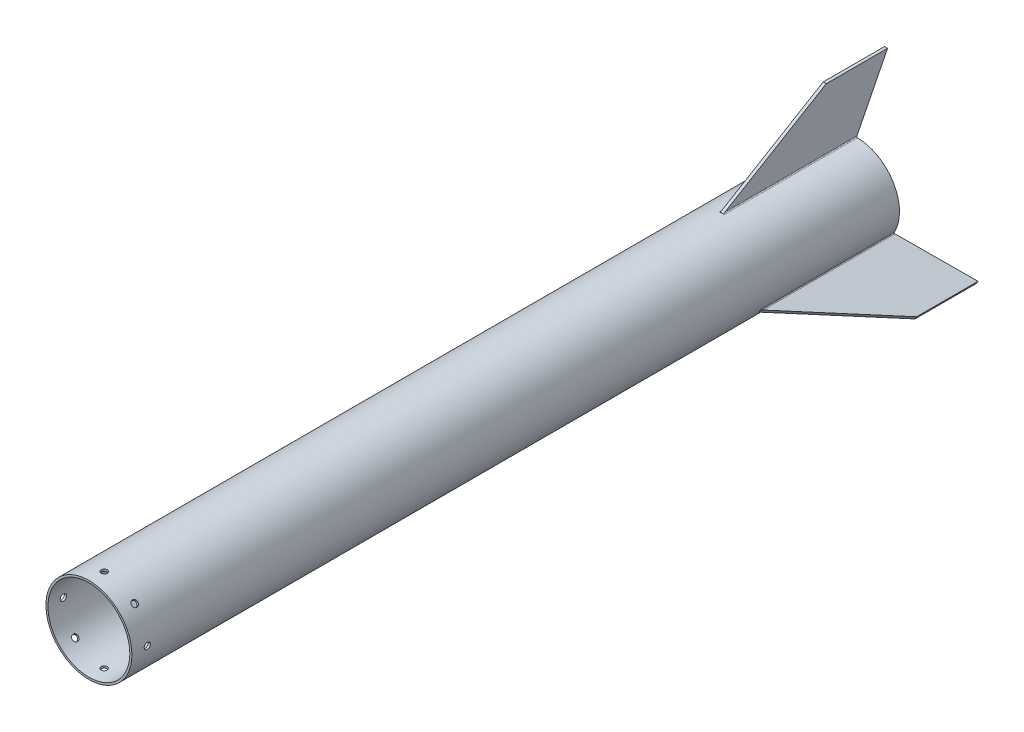
SolidWorks part; units mm, degrees
material "Default"
ref_plane "Front Plane" through (0, 0, 0) normal (0, 0, 1) x (1, 0, 0)
ref_plane "Top Plane" through (0, 0, 0) normal (0, 1, 0) x (1, 0, 0)
ref_plane "Right Plane" through (0, 0, 0) normal (1, 0, 0) x (0, 0, -1)
sketch "Sketch1" plane through (0, 0, 0) normal (0, 0, 1) x (1, 0, 0)
  circle A0 centre (0, 0) radius 42
  circle A1 centre (0, 0) radius 40
  dimension "D1" = 84
  dimension "D2" = 2
extrude "Boss-Extrude1" add sketch "Sketch1" along normal blind 750
ref_plane "Bolts to Avionics" through (45, 0, 0) normal (1, 0, 0) x (0, 0, -1)
ref_plane "Tail bolts" through (-40, 0, 0) normal (1, 0, 0) x (0, 0, -1)
sketch "Sketch2" plane through (45, 0, 0) normal (1, 0, 0) x (0, 0, -1)
  line L0 (-750, 0) -> (-735, 0) construction
  line L1 (-750, 42) -> (-750, -42) construction
  circle A0 centre (-735, 0) radius 3
  dimension "D2" = 6
  dimension "D1" = 15
extrude "Cut-Extrude1" cut sketch "Sketch2" against normal up to surface (5 mm away) up to face at (40, 0, 750)
pattern_circular "CirPattern1" count 8 over 360 about axis through (0, 0, 750) along (0, 0, -1) of "Cut-Extrude1"
sketch "Sketch4" plane through (-40, 0, 0) normal (1, 0, 0) x (0, 0, -1)
  line L0 (0, 0) -> (-20, 0) construction
  circle A0 centre (-20, 0) radius 5
  dimension "D2" = 10
  dimension "D1" = 20
extrude "Cut-Extrude2" cut sketch "Sketch4" along normal up to surface up to face at (-2.9218, -39.8931, 734.3195)
pattern_circular "CirPattern2" count 6 over 360 about axis through (0, 0, 0) along (0, 0, 1) of "Cut-Extrude2"
sketch "Tail Configuration" plane through (0, 0, 0) normal (0, 0, -1) x (-1, 0, 0)
  line L0 (0, 0) -> (0, 42) construction
  line L1 (0, 0) -> (36.3731, -21) construction
  line L2 (0, 0) -> (-36.3731, -21) construction
  line L3 (31.4856, -29.4654) -> (41.2605, -12.5346) construction
  line L4 (-41.8479, -11.5173) -> (-30.8983, -30.4827) construction
  circle A0 centre (0, 0) radius 42 construction
  point P10 (0, 0)
  point P12 (36.3731, -21)
  point P15 (-36.3731, -21)
  dimension "D1" = 3
ref_plane "Fin 1" through (0, 42, 0) normal (0, 1, 0) x (1, 0, 0)
sketch "Sketch6" plane through (0, 42, 0) normal (0, 1, 0) x (1, 0, 0)
  line L4 (0, 0) -> (0, -62.2364) construction
  point P4 (0, 0)
ref_plane "Plane6" through (0, 0, 0) normal (-1, 0, 0) x (0, 0, 1)
sketch "Sketch13" plane through (0, 0, 0) normal (-1, 0, 0) x (0, 0, 1)
  line L0 (0, 42) -> (130, 42) construction
  line L1 (52.1788, 42) -> (-52.1788, 42) construction
  line L2 (130, 42) -> (29.6133, 102)
  line L3 (29.6133, 102) -> (-30.3867, 102)
  line L4 (-30.3867, 102) -> (0, 42)
  line L5 (0, 42) -> (0, 102) construction
  line L6 (97.5, 42) -> (97.5, 50.3814) construction
  line L7 (97.5, 42) -> (14.6133, 102) construction
  line L9 (0, 42) -> (130, 42) construction
  line L10 (0, 42) -> (0, 41)
  line L11 (0, 41) -> (130, 41)
  line L12 (130, 42) -> (130, 41)
  dimension "D5" = 32.5
  dimension "D6" = 15
  dimension "D7" = 1
  dimension "D1" = 60
  dimension "D2" = 130
  dimension "D3" = 60
  dimension "D4" = 54.1
extrude "Boss-Extrude6" add sketch "Sketch13" along normal blind 3
ref_plane "Fin 2" through (-36.3731, -21, 0) normal (0.866, 0.5, 0) x (-0.5, 0.866, 0)
sketch "Sketch9" plane through (-36.3731, -21, 0) normal (0.866, 0.5, 0) x (-0.5, 0.866, 0)
  line L0 (0, 0) -> (0, 21.8091) construction
ref_plane "Plane4" through (0, 0, 0) normal (-0.5, 0.866, 0) x (0, 0, 1)
sketch "Sketch10" plane through (0, 0, 0) normal (-0.5, 0.866, 0) x (0, 0, 1)
  line L0 (0, -42) -> (-30.3867, -102)
  line L1 (-30.3867, -102) -> (29.6133, -102)
  line L2 (29.6133, -102) -> (130, -42)
  line L3 (0, -42) -> (750, -42) construction
  line L4 (130, -42) -> (0, -42) construction
  line L5 (97.5, -42) -> (97.5, -62.2562) construction
  line L6 (97.5, -42) -> (14.6133, -102) construction
  line L7 (0, -42) -> (0, -102) construction
  line L9 (0, -42) -> (130, -42) construction
  line L10 (0, -42) -> (0, -41)
  line L11 (0, -41) -> (130, -41)
  line L12 (130, -42) -> (130, -41)
  dimension "D1" = 130
  dimension "D3" = 54.1
  dimension "D4" = 60
  dimension "D2" = 60
  dimension "D5" = 32.5
  dimension "D6" = 15
  dimension "D7" = 1
extrude "Boss-Extrude7" add sketch "Sketch10" along normal blind 3
ref_plane "Fin 3" through (36.3731, -21, 0) normal (-0.866, 0.5, 0) x (-0.5, -0.866, 0)
sketch "Sketch11" plane through (36.3731, -21, 0) normal (-0.866, 0.5, 0) x (-0.5, -0.866, 0)
  line L0 (0, 0) -> (0, 29.9322) construction
ref_plane "Plane5" through (0, 0, 0) normal (-0.5, -0.866, 0) x (0, 0, 1)
sketch "Sketch12" plane through (0, 0, 0) normal (-0.5, -0.866, 0) x (0, 0, 1)
  line L0 (0, -42) -> (130, -42) construction
  line L1 (0, -42) -> (750, -42) construction
  line L2 (130, -42) -> (29.6133, -102)
  line L3 (29.6133, -102) -> (-30.3867, -102)
  line L4 (-30.3867, -102) -> (0, -42)
  line L5 (0, -42) -> (0, -102) construction
  line L6 (97.5, -42) -> (97.5, -53.3564) construction
  line L7 (97.5, -42) -> (14.6133, -102) construction
  line L9 (0, -42) -> (130, -42) construction
  line L10 (0, -42) -> (0, -41)
  line L11 (0, -41) -> (130, -41)
  line L12 (130, -42) -> (130, -41)
  dimension "D1" = 130
  dimension "D3" = 54.1
  dimension "D2" = 60
  dimension "D5" = 32.5
  dimension "D7" = 1
  dimension "D4" = 15
  dimension "D6" = 60
extrude "Boss-Extrude5" add sketch "Sketch12" along normal blind 3
fillet "Fillet5" radius 1 6 edges at (-3, 41.8927, 65) (0, 42, 65) (-36.3731, -21, 65) (-37.7802, -18.3483, 65) (36.3731, -21, 65) (34.7802, -23.5444, 65)
equation "\"Tip Chord\"= 60mm"
equation "\"Root Chord\"= 130mm"
equation "\"Height\"= 60mm"
equation "\"Sweep angle\"= 54.1deg"
equation "\"D1@Sketch10\"=\"Root Chord\""
equation "\"D3@Sketch10\"=\"Sweep angle\""
equation "\"D4@Sketch10\"=\"Height\""
equation "\"D2@Sketch10\"=\"Tip Chord\""
equation "\"D1@Sketch12\"=\"Root Chord\""
equation "\"D2@Sketch12\"=\"Height\""
equation "\"D3@Sketch12\"=\"Sweep angle\""
equation "\"D4@Sketch12\"=\"Tip Chord\"/4"
equation "\"D5@Sketch12\"=\"Root Chord\"/4"
equation "\"D6@Sketch12\"=\"Tip Chord\""
equation "\"D5@Sketch10\"=\"Root Chord\"/4"
equation "\"D6@Sketch10\"=\"Tip Chord\"/4"
equation "\"D1@Sketch13\"=\"Height\""
equation "\"D2@Sketch13\"=\"Root Chord\""
equation "\"D3@Sketch13\"=\"Tip Chord\""
equation "\"D4@Sketch13\"=\"Sweep angle\""
equation "\"D5@Sketch13\"=\"Root Chord\"/4"
equation "\"D6@Sketch13\"=\"Tip Chord\"/4"
